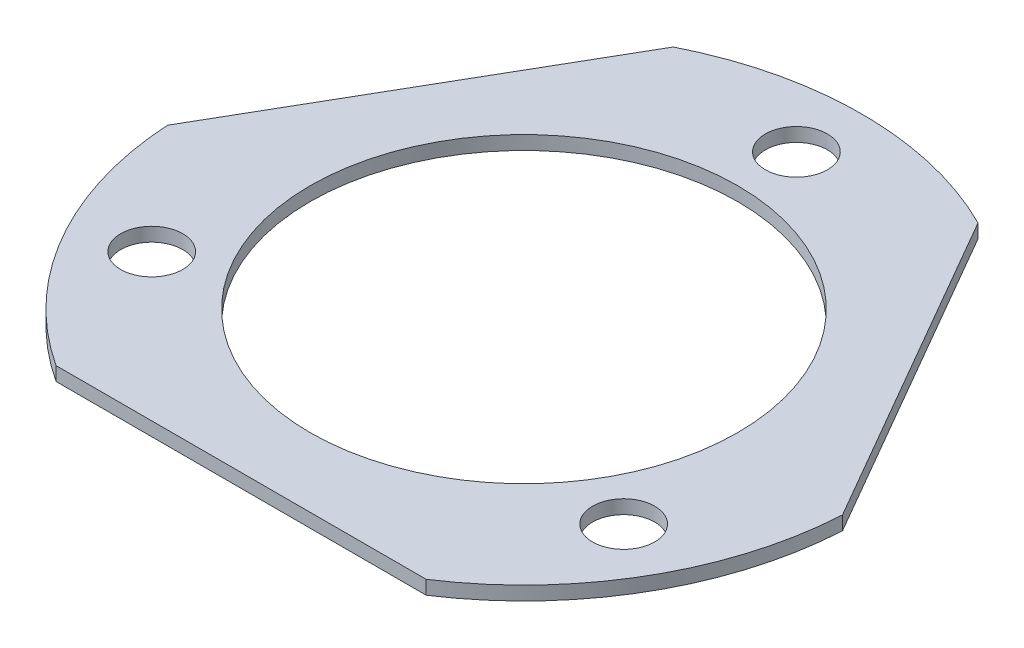
SolidWorks part; units mm, degrees
material "ASTM A36"
ref_plane "Plano frontal" through (0, 0, 0) normal (0, 0, 1) x (1, 0, 0)
ref_plane "Plano superior" through (0, 0, 0) normal (0, 1, 0) x (1, 0, 0)
ref_plane "Plano direito" through (0, 0, 0) normal (1, 0, 0) x (0, 0, -1)
sketch "Esboço1" plane through (0, 0, 0) normal (0, 1, 0) x (1, 0, 0)
  line L0 (-22.0906, 43.7379) -> (-48.9234, -2.7379)
  line L1 (48.9234, -2.7379) -> (22.0906, 43.7379)
  line L2 (-26.8328, -41) -> (26.8328, -41)
  line L3 (0, 35) -> (0, 31) construction
  line L4 (0, 0) -> (-26.8468, 15.5) construction
  line L5 (-26.8468, 15.5) -> (-35.507, 20.5) construction
  circle A0 centre (0, 0) radius 31
  circle A1 centre (0, 0) radius 39.5 construction
  arc A2 (-48.9234, -2.7379) -> (-26.8328, -41) centre (0, 0) ccw
  circle A3 centre (0, 39.5) radius 4.5
  circle A4 centre (34.208, -19.75) radius 4.5
  circle A5 centre (-34.208, -19.75) radius 4.5
  arc A6 (22.0906, 43.7379) -> (-22.0906, 43.7379) centre (0, 0) ccw
  arc A7 (26.8328, -41) -> (48.9234, -2.7379) centre (0, 0) ccw
  point P19 (0, 0)
  dimension "D2" = 62
  dimension "D3" = 18
  dimension "D4" = 9
  dimension "D5" = 79
  dimension "D6" = 10
  dimension "D1" = 3
base flange "Flange-base1" sketch "Esboço1" thickness 2 reverse thickness direction no parameters "D1"=6
sketch "Curva-Linhas1" [suppressed] plane through (0, 0, 0) normal (0, 1, 0) x (1, 0, 0)
sketch "Caixa delimitadora1" [suppressed] plane through (0, 0, 0) normal (0, 1, 0) x (1, 0, 0)
sheet metal parameters "Chapa metálica3" thickness 2 parameters "D1"=6
flat pattern "Padrão-Plano3" [suppressed]
sketch "Curva-Linhas2" plane through (0, 0, 0) normal (0, 1, 0) x (1, 0, 0)
sketch3d "Caixa delimitadora2" [suppressed]
  line L0 (-48.9234, -41, 0) -> (48.9234, -41, 0) construction
  line L1 (-48.9234, 49, 0) -> (48.9234, 49, 0) construction
  line L2 (-48.9234, -41, 0) -> (-48.9234, 49, 0) construction
  line L3 (48.9234, -41, 0) -> (48.9234, 49, 0) construction
